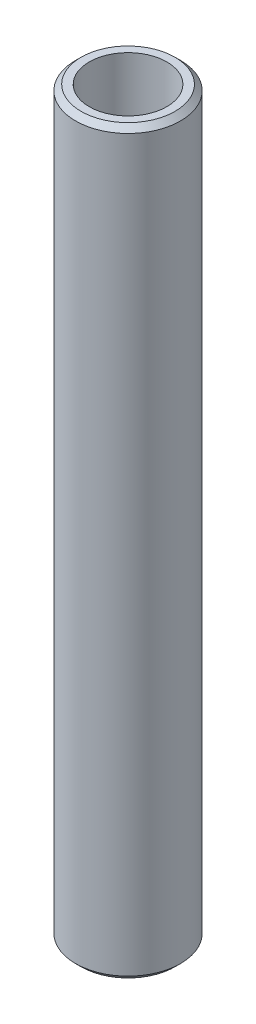
SolidWorks part; units mm, degrees
ref_plane "Front Plane" through (0, 0, 0) normal (0, 0, 1) x (1, 0, 0)
ref_plane "Top Plane" through (0, 0, 0) normal (0, 1, 0) x (1, 0, 0)
ref_plane "Right Plane" through (0, 0, 0) normal (1, 0, 0) x (0, 0, -1)
sketch "Sketch1" plane through (0, 0, 0) normal (0, 1, 0) x (1, 0, 0)
  circle A0 centre (0, 0) radius 42.5
  dimension "SHAFT_OD" = 85
extrude "Boss-Extrude1" add sketch "Sketch1" along normal blind 600
sketch "Sketch2" plane through (0, 0, 0) normal (0, 1, 0) x (1, 0, 0)
  circle A0 centre (0, 0) radius 31.4378
  dimension "BORE_D" = 62.8755
extrude "Cut-Extrude1" cut sketch "Sketch2" along normal through all
chamfer "Chamfer1" distance 4.4686 angle 45 2 edges at (0, 600, 42.5) (0, 0, 42.5)
